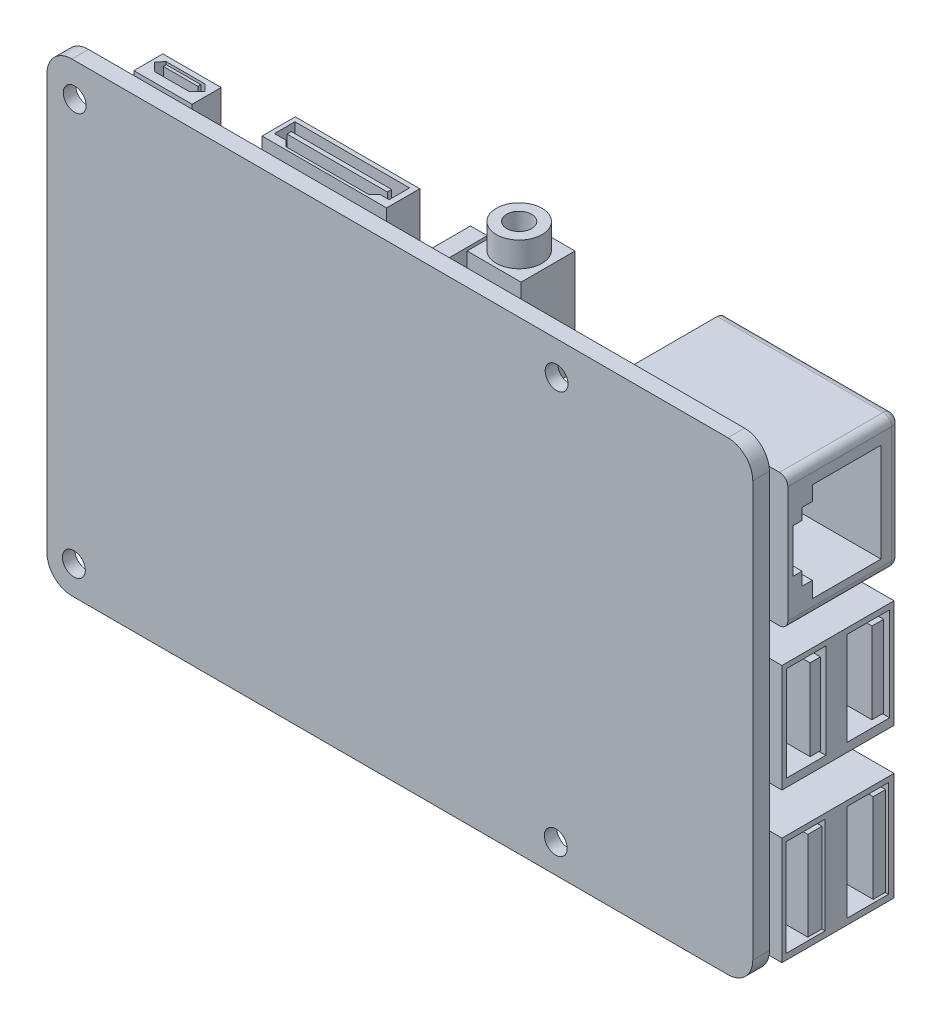
SolidWorks part; units mm, degrees
ref_plane "Front Plane" through (0, 0, 0) normal (0, 0, 1) x (1, 0, 0)
ref_plane "Top Plane" through (0, 0, 0) normal (0, 1, 0) x (1, 0, 0)
ref_plane "Right Plane" through (0, 0, 0) normal (1, 0, 0) x (0, 0, -1)
sketch "Sketch1" plane through (0, 0, 0) normal (0, 0, 1) x (1, 0, 0)
  line L1 (-42.5, 28) -> (42.5, 28)
  line L2 (-42.5, 28) -> (-42.5, -28)
  line L3 (-42.5, -28) -> (42.5, -28)
  line L4 (42.5, 28) -> (42.5, -28)
  line L5 (-42.5, 28) -> (42.5, -28) construction
  line L6 (-42.5, -28) -> (42.5, 28) construction
  point P0 (0, 0)
  dimension "D1" = 85
  dimension "D2" = 56
extrude "Boss-Extrude1" add sketch "Sketch1" along normal blind 2
fillet "Fillet1" radius 3 4 edges at (42.5, -28, 1) (42.5, 28, 1) (-42.5, 28, 1) (-42.5, -28, 1)
sketch "Sketch2" plane through (0, 0, 0) normal (0, 0, -1) x (-1, 0, 0)
  circle A0 centre (39.161, -24.5985) radius 3.1
  circle A1 centre (-18.839, -24.5986) radius 3.1
  circle A2 centre (39.161, 23.9785) radius 3.1
  circle A3 centre (-18.839, 23.9761) radius 3.1
  dimension "D1" = 6.2
  dimension "D3" = 6.2
  dimension "D2" = 58
  dimension "D4" = 58
extrude "Cut-Extrude2" cut sketch "Sketch2" against normal blind 0.5
sketch "Sketch3" plane through (0, 0, 0.5) normal (0, 0, -1) x (-1, 0, 0)
  circle A0 centre (39.161, 23.9785) radius 1.375
  circle A1 centre (-18.8764, 23.9785) radius 1.375
  circle A2 centre (-18.7753, -24.5312) radius 1.375
  circle A3 centre (39.2622, -24.5312) radius 1.375
  dimension "D1" = 2.75
  dimension "D2" = 2.75
extrude "Cut-Extrude3" cut sketch "Sketch3" against normal blind 10.5
sketch "Sketch4" plane through (0, 0, 0) normal (0, 0, -1) x (-1, 0, 0)
  line L0 (-39.5, 28) -> (39.5, 28) construction
  line L1 (-23.7207, 9.5) -> (-44.7207, 9.5)
  line L2 (-23.7207, 9.5) -> (-23.7207, 25.5)
  line L3 (-23.7207, 25.5) -> (-44.7207, 25.5)
  line L4 (-44.7207, 9.5) -> (-44.7207, 25.5)
  line L5 (-23.7207, 9.5) -> (-44.7207, 25.5) construction
  line L6 (-23.7207, 25.5) -> (-44.7207, 9.5) construction
  point P0 (-34.2207, 17.5)
  dimension "D1" = 2.5
  dimension "D2" = 21
  dimension "D3" = 16
  dimension "D4" = 10.5
extrude "Boss-Extrude2" add sketch "Sketch4" along normal blind 13.5
fillet "Fillet2" radius 1 5 edges at (34.2207, 25.5, -13.5) (34.2207, 9.5, -13.5) (44.7207, 9.5, -6.75) (44.7207, 25.5, -6.75) (44.7207, 17.5, -13.5)
sketch "Sketch5" plane through (44.7207, 0, 0) normal (1, 0, 0) x (0, 0, -1)
  line L0 (0.6237, 20.117) -> (0.6237, 14.8349)
  line L1 (0.6237, 14.8349) -> (1.7111, 14.8349)
  line L2 (1.7111, 14.8349) -> (1.7111, 13.2605)
  line L3 (1.7111, 13.2605) -> (2.9538, 13.2605)
  line L4 (2.9538, 13.2605) -> (2.9538, 11.3427)
  line L5 (2.9538, 11.3427) -> (11.2173, 11.3427)
  line L6 (11.2173, 11.3427) -> (11.2173, 23.2197)
  line L7 (11.2173, 23.2197) -> (2.9538, 23.2197)
  line L8 (2.9538, 23.2197) -> (2.9538, 21.4786)
  line L9 (2.9538, 21.4786) -> (1.7111, 21.4786)
  line L10 (1.7111, 21.4786) -> (1.7111, 20.117)
  line L11 (1.7111, 20.117) -> (0.6237, 20.117)
extrude "Cut-Extrude4" cut sketch "Sketch5" against normal blind 18.5
sketch "Sketch7" plane through (0, 0, 0) normal (0, 0, -1) x (-1, 0, 0)
  line L0 (-39.5, 28) -> (39.5, 28) construction
  line L1 (-44.0111, 5.5) -> (-27.0111, 5.5)
  line L2 (-44.0111, 5.5) -> (-44.0111, -7.5)
  line L3 (-44.0111, -7.5) -> (-27.0111, -7.5)
  line L4 (-27.0111, 5.5) -> (-27.0111, -7.5)
  line L5 (-44.0111, 5.5) -> (-27.0111, -7.5) construction
  line L6 (-44.0111, -7.5) -> (-27.0111, 5.5) construction
  point P0 (-35.5111, -1)
  dimension "D1" = 29
  dimension "D2" = 13
  dimension "D3" = 17
extrude "Boss-Extrude3" add sketch "Sketch7" along normal blind 13.5
sketch "Sketch8" plane through (44.0111, 0, 0) normal (1, 0, 0) x (0, 0, -1)
  line L1 (7.8471, 4.8156) -> (12.9735, 4.8156)
  line L2 (7.8471, 4.8156) -> (7.8471, -6.4468)
  line L3 (7.8471, -6.4468) -> (12.9735, -6.4468)
  line L4 (12.9735, 4.8156) -> (12.9735, -6.4468)
  line L5 (7.8471, 4.8156) -> (12.9735, -6.4468) construction
  line L6 (7.8471, -6.4468) -> (12.9735, 4.8156) construction
  line L7 (0.546, 4.8933) -> (5.284, 4.8933)
  line L8 (0.546, 4.8933) -> (0.546, -6.5244)
  line L9 (0.546, -6.5244) -> (5.284, -6.5244)
  line L10 (5.284, 4.8933) -> (5.284, -6.5244)
  line L11 (0.546, 4.8933) -> (5.284, -6.5244) construction
  line L12 (0.546, -6.5244) -> (5.284, 4.8933) construction
  point P0 (10.4103, -0.8156)
  point P5 (2.915, -0.8156)
extrude "Cut-Extrude5" cut sketch "Sketch8" against normal blind 13.5
sketch "Sketch9" plane through (30.5111, 0, 0) normal (1, 0, 0) x (0, 0, -1)
  line L1 (10.8479, 4.1943) -> (12.246, 4.1943)
  line L2 (10.8479, 4.1943) -> (10.8479, -5.5924)
  line L3 (10.8479, -5.5924) -> (12.246, -5.5924)
  line L4 (12.246, 4.1943) -> (12.246, -5.5924)
  line L5 (10.8479, 4.1943) -> (12.246, -5.5924) construction
  line L6 (10.8479, -5.5924) -> (12.246, 4.1943) construction
  line L7 (3.3914, 4.0778) -> (4.6341, 4.0778)
  line L8 (3.3914, 4.0778) -> (3.3914, -5.7089)
  line L9 (3.3914, -5.7089) -> (4.6341, -5.7089)
  line L10 (4.6341, 4.0778) -> (4.6341, -5.7089)
  line L11 (3.3914, 4.0778) -> (4.6341, -5.7089) construction
  line L12 (3.3914, -5.7089) -> (4.6341, 4.0778) construction
  point P0 (11.5469, -0.699)
  point P5 (4.0128, -0.8156)
  dimension "D1" = 0.6214
extrude "Boss-Extrude4" add sketch "Sketch9" along normal blind 13.5
sketch "Sketch10" plane through (0, 0, 0) normal (0, 0, -1) x (-1, 0, 0)
  line L0 (-39.5, 28) -> (39.5, 28) construction
  line L1 (-44.0178, -12.5) -> (-27.0044, -12.5)
  line L2 (-44.0178, -12.5) -> (-44.0178, -25.5)
  line L3 (-44.0178, -25.5) -> (-27.0044, -25.5)
  line L4 (-27.0044, -12.5) -> (-27.0044, -25.5)
  line L5 (-44.0178, -12.5) -> (-27.0044, -25.5) construction
  line L6 (-44.0178, -25.5) -> (-27.0044, -12.5) construction
  point P0 (-35.5111, -19)
  dimension "D1" = 47
  dimension "D2" = 13
  dimension "D3" = 17.0134
extrude "Boss-Extrude5" add sketch "Sketch10" along normal blind 13.5
sketch "Sketch11" plane through (44.0178, 0, 0) normal (1, 0, 0) x (0, 0, -1)
  line L1 (7.8471, -13.1265) -> (12.8181, -13.1265)
  line L2 (7.8471, -13.1265) -> (7.8471, -24.7773)
  line L3 (7.8471, -24.7773) -> (12.8181, -24.7773)
  line L4 (12.8181, -13.1265) -> (12.8181, -24.7773)
  line L5 (7.8471, -13.1265) -> (12.8181, -24.7773) construction
  line L6 (7.8471, -24.7773) -> (12.8181, -13.1265) construction
  line L7 (0.4891, -13.1265) -> (5.2063, -13.1265)
  line L8 (0.4891, -13.1265) -> (0.4891, -24.7773)
  line L9 (0.4891, -24.7773) -> (5.2063, -24.7773)
  line L10 (5.2063, -13.1265) -> (5.2063, -24.7773)
  line L11 (0.4891, -13.1265) -> (5.2063, -24.7773) construction
  line L12 (0.4891, -24.7773) -> (5.2063, -13.1265) construction
  point P0 (10.3326, -18.9519)
  point P5 (2.8477, -18.9519)
extrude "Cut-Extrude6" cut sketch "Sketch11" against normal blind 13.5
sketch "Sketch12" plane through (30.5178, 0, 0) normal (1, 0, 0) x (0, 0, -1)
  line L1 (12.479, -13.6702) -> (10.9825, -13.6702)
  line L2 (12.479, -13.6702) -> (12.479, -24.3889)
  line L3 (12.479, -24.3889) -> (10.9825, -24.3889)
  line L4 (10.9825, -13.6702) -> (10.9825, -24.3889)
  line L5 (12.479, -13.6702) -> (10.9825, -24.3889) construction
  line L6 (12.479, -24.3889) -> (10.9825, -13.6702) construction
  line L7 (3.1092, -13.6702) -> (4.8168, -13.6702)
  line L8 (3.1092, -13.6702) -> (3.1092, -24.3889)
  line L9 (3.1092, -24.3889) -> (4.8168, -24.3889)
  line L10 (4.8168, -13.6702) -> (4.8168, -24.3889)
  line L11 (3.1092, -13.6702) -> (4.8168, -24.3889) construction
  line L12 (3.1092, -24.3889) -> (4.8168, -13.6702) construction
  point P0 (11.7307, -19.0296)
  point P6 (3.963, -19.0296)
extrude "Boss-Extrude6" add sketch "Sketch12" along normal blind 13.5
sketch "Sketch13" plane through (0, 0, 0) normal (0, 0, -1) x (-1, 0, 0)
  line L0 (42.5, 25) -> (42.5, -25) construction
  line L1 (-14.0854, -22.7565) -> (35.0854, -22.7565)
  line L2 (-14.0854, -22.7565) -> (-14.0854, -27.2565)
  line L3 (-14.0854, -27.2565) -> (35.0854, -27.2565)
  line L4 (35.0854, -22.7565) -> (35.0854, -27.2565)
  line L5 (-14.0854, -22.7565) -> (35.0854, -27.2565) construction
  line L6 (-14.0854, -27.2565) -> (35.0854, -22.7565) construction
  point P0 (10.5, -25.0065)
  dimension "D1" = 32
  dimension "D2" = 4.5
extrude "Boss-Extrude7" add sketch "Sketch13" along normal blind 2.5
sketch "Sketch14" plane through (0, 0, -2.5) normal (0, 0, -1) x (-1, 0, 0)
  line L0 (-11.0708, -26.0079) -> (-10.1069, -26.0079)
  line L1 (-13.5708, -26.0079) -> (-12.6069, -26.0079)
  line L2 (-13.5708, -26.0079) -> (-13.5708, -27.0079)
  line L3 (-13.5708, -27.0079) -> (-12.6069, -27.0079)
  line L4 (-12.6069, -26.0079) -> (-12.6069, -27.0079)
  line L5 (-13.5708, -26.0079) -> (-12.6069, -27.0079) construction
  line L6 (-13.5708, -27.0079) -> (-12.6069, -26.0079) construction
  line L7 (-10.1069, -26.0079) -> (-10.1069, -27.0079)
  line L8 (-11.0708, -27.0079) -> (-10.1069, -27.0079)
  line L9 (-11.0708, -26.0079) -> (-11.0708, -27.0079)
  line L10 (-8.5708, -26.0079) -> (-7.6069, -26.0079)
  line L11 (-7.6069, -26.0079) -> (-7.6069, -27.0079)
  line L12 (-8.5708, -27.0079) -> (-7.6069, -27.0079)
  line L13 (-8.5708, -26.0079) -> (-8.5708, -27.0079)
  line L14 (-6.0708, -26.0079) -> (-5.1069, -26.0079)
  line L15 (-5.1069, -26.0079) -> (-5.1069, -27.0079)
  line L16 (-6.0708, -27.0079) -> (-5.1069, -27.0079)
  line L17 (-6.0708, -26.0079) -> (-6.0708, -27.0079)
  line L18 (-3.5708, -26.0079) -> (-2.6069, -26.0079)
  line L19 (-2.6069, -26.0079) -> (-2.6069, -27.0079)
  line L20 (-3.5708, -27.0079) -> (-2.6069, -27.0079)
  line L21 (-3.5708, -26.0079) -> (-3.5708, -27.0079)
  line L22 (-1.0708, -26.0079) -> (-0.1069, -26.0079)
  line L23 (-0.1069, -26.0079) -> (-0.1069, -27.0079)
  line L24 (-1.0708, -27.0079) -> (-0.1069, -27.0079)
  line L25 (-1.0708, -26.0079) -> (-1.0708, -27.0079)
  line L26 (1.4292, -26.0079) -> (2.3931, -26.0079)
  line L27 (2.3931, -26.0079) -> (2.3931, -27.0079)
  line L28 (1.4292, -27.0079) -> (2.3931, -27.0079)
  line L29 (1.4292, -26.0079) -> (1.4292, -27.0079)
  line L30 (3.9292, -26.0079) -> (4.8931, -26.0079)
  line L31 (4.8931, -26.0079) -> (4.8931, -27.0079)
  line L32 (3.9292, -27.0079) -> (4.8931, -27.0079)
  line L33 (3.9292, -26.0079) -> (3.9292, -27.0079)
  line L34 (6.4292, -26.0079) -> (7.3931, -26.0079)
  line L35 (7.3931, -26.0079) -> (7.3931, -27.0079)
  line L36 (6.4292, -27.0079) -> (7.3931, -27.0079)
  line L37 (6.4292, -26.0079) -> (6.4292, -27.0079)
  line L38 (8.9292, -26.0079) -> (9.8931, -26.0079)
  line L39 (9.8931, -26.0079) -> (9.8931, -27.0079)
  line L40 (8.9292, -27.0079) -> (9.8931, -27.0079)
  line L41 (8.9292, -26.0079) -> (8.9292, -27.0079)
  line L42 (11.4292, -26.0079) -> (12.3931, -26.0079)
  line L43 (12.3931, -26.0079) -> (12.3931, -27.0079)
  line L44 (11.4292, -27.0079) -> (12.3931, -27.0079)
  line L45 (11.4292, -26.0079) -> (11.4292, -27.0079)
  line L46 (13.9292, -26.0079) -> (14.8931, -26.0079)
  line L47 (14.8931, -26.0079) -> (14.8931, -27.0079)
  line L48 (13.9292, -27.0079) -> (14.8931, -27.0079)
  line L49 (13.9292, -26.0079) -> (13.9292, -27.0079)
  line L50 (16.4292, -26.0079) -> (17.3931, -26.0079)
  line L51 (17.3931, -26.0079) -> (17.3931, -27.0079)
  line L52 (16.4292, -27.0079) -> (17.3931, -27.0079)
  line L53 (16.4292, -26.0079) -> (16.4292, -27.0079)
  line L54 (18.9292, -26.0079) -> (19.8931, -26.0079)
  line L55 (19.8931, -26.0079) -> (19.8931, -27.0079)
  line L56 (18.9292, -27.0079) -> (19.8931, -27.0079)
  line L57 (18.9292, -26.0079) -> (18.9292, -27.0079)
  line L58 (21.4292, -26.0079) -> (22.3931, -26.0079)
  line L59 (22.3931, -26.0079) -> (22.3931, -27.0079)
  line L60 (21.4292, -27.0079) -> (22.3931, -27.0079)
  line L61 (21.4292, -26.0079) -> (21.4292, -27.0079)
  line L62 (23.9292, -26.0079) -> (24.8931, -26.0079)
  line L63 (24.8931, -26.0079) -> (24.8931, -27.0079)
  line L64 (23.9292, -27.0079) -> (24.8931, -27.0079)
  line L65 (23.9292, -26.0079) -> (23.9292, -27.0079)
  line L66 (26.4292, -26.0079) -> (27.3931, -26.0079)
  line L67 (27.3931, -26.0079) -> (27.3931, -27.0079)
  line L68 (26.4292, -27.0079) -> (27.3931, -27.0079)
  line L69 (26.4292, -26.0079) -> (26.4292, -27.0079)
  line L70 (28.9292, -26.0079) -> (29.8931, -26.0079)
  line L71 (29.8931, -26.0079) -> (29.8931, -27.0079)
  line L72 (28.9292, -27.0079) -> (29.8931, -27.0079)
  line L73 (28.9292, -26.0079) -> (28.9292, -27.0079)
  line L74 (31.4292, -26.0079) -> (32.3931, -26.0079)
  line L75 (32.3931, -26.0079) -> (32.3931, -27.0079)
  line L76 (31.4292, -27.0079) -> (32.3931, -27.0079)
  line L77 (31.4292, -26.0079) -> (31.4292, -27.0079)
  line L78 (33.9292, -26.0079) -> (34.8931, -26.0079)
  line L79 (34.8931, -26.0079) -> (34.8931, -27.0079)
  line L80 (33.9292, -27.0079) -> (34.8931, -27.0079)
  line L81 (33.9292, -26.0079) -> (33.9292, -27.0079)
  line L82 (1.4292, -23.0147) -> (1.4292, -24.0147)
  line L83 (26.4292, -23.0147) -> (27.3931, -23.0147)
  line L84 (31.4292, -23.0147) -> (32.3931, -23.0147)
  line L85 (-7.6069, -23.0147) -> (-7.6069, -24.0147)
  line L86 (-3.5708, -24.0147) -> (-2.6069, -24.0147)
  line L87 (-1.0708, -23.0147) -> (-1.0708, -24.0147)
  line L88 (8.9292, -23.0147) -> (9.8931, -23.0147)
  line L89 (13.9292, -23.0147) -> (14.8931, -23.0147)
  line L90 (13.9292, -24.0147) -> (14.8931, -24.0147)
  line L91 (16.4292, -23.0147) -> (17.3931, -23.0147)
  line L92 (11.4292, -23.0147) -> (11.4292, -24.0147)
  line L93 (21.4292, -24.0147) -> (22.3931, -24.0147)
  line L94 (34.8931, -23.0147) -> (34.8931, -24.0147)
  line L95 (-11.0708, -24.0147) -> (-10.1069, -24.0147)
  line L96 (-0.1069, -23.0147) -> (-0.1069, -24.0147)
  line L97 (6.4292, -24.0147) -> (7.3931, -24.0147)
  line L98 (21.4292, -23.0147) -> (21.4292, -24.0147)
  line L99 (27.3931, -23.0147) -> (27.3931, -24.0147)
  line L100 (3.9292, -23.0147) -> (4.8931, -23.0147)
  line L101 (16.4292, -23.0147) -> (16.4292, -24.0147)
  line L102 (32.3931, -23.0147) -> (32.3931, -24.0147)
  line L103 (-13.5708, -23.0147) -> (-12.6069, -23.0147)
  line L104 (3.9292, -24.0147) -> (4.8931, -24.0147)
  line L105 (3.9292, -23.0147) -> (3.9292, -24.0147)
  line L106 (11.4292, -23.0147) -> (12.3931, -23.0147)
  line L107 (11.4292, -24.0147) -> (12.3931, -24.0147)
  line L108 (18.9292, -23.0147) -> (18.9292, -24.0147)
  line L109 (26.4292, -23.0147) -> (26.4292, -24.0147)
  line L110 (-13.5708, -24.0147) -> (-12.6069, -24.0147)
  line L111 (-5.1069, -23.0147) -> (-5.1069, -24.0147)
  line L112 (21.4292, -23.0147) -> (22.3931, -23.0147)
  line L113 (26.4292, -24.0147) -> (27.3931, -24.0147)
  line L114 (-2.6069, -23.0147) -> (-2.6069, -24.0147)
  line L115 (1.4292, -24.0147) -> (2.3931, -24.0147)
  line L116 (6.4292, -23.0147) -> (7.3931, -23.0147)
  line L117 (8.9292, -23.0147) -> (8.9292, -24.0147)
  line L118 (23.9292, -23.0147) -> (23.9292, -24.0147)
  line L119 (28.9292, -23.0147) -> (29.8931, -23.0147)
  line L120 (-13.5708, -23.0147) -> (-12.6069, -24.0147) construction
  line L121 (-11.0708, -23.0147) -> (-11.0708, -24.0147)
  line L122 (-8.5708, -24.0147) -> (-7.6069, -24.0147)
  line L123 (-6.0708, -23.0147) -> (-6.0708, -24.0147)
  line L124 (-1.0708, -24.0147) -> (-0.1069, -24.0147)
  line L125 (6.4292, -23.0147) -> (6.4292, -24.0147)
  line L126 (8.9292, -24.0147) -> (9.8931, -24.0147)
  line L127 (24.8931, -23.0147) -> (24.8931, -24.0147)
  line L128 (33.9292, -24.0147) -> (34.8931, -24.0147)
  line L129 (18.9292, -23.0147) -> (19.8931, -23.0147)
  line L130 (31.4292, -23.0147) -> (31.4292, -24.0147)
  line L131 (-10.1069, -23.0147) -> (-10.1069, -24.0147)
  line L132 (-3.5708, -23.0147) -> (-3.5708, -24.0147)
  line L133 (7.3931, -23.0147) -> (7.3931, -24.0147)
  line L134 (12.3931, -23.0147) -> (12.3931, -24.0147)
  line L135 (13.9292, -23.0147) -> (13.9292, -24.0147)
  line L136 (23.9292, -23.0147) -> (24.8931, -23.0147)
  line L137 (-12.6069, -23.0147) -> (-12.6069, -24.0147)
  line L138 (16.4292, -24.0147) -> (17.3931, -24.0147)
  line L139 (29.8931, -23.0147) -> (29.8931, -24.0147)
  line L140 (-11.0708, -23.0147) -> (-10.1069, -23.0147)
  line L141 (-6.0708, -23.0147) -> (-5.1069, -23.0147)
  line L142 (9.8931, -23.0147) -> (9.8931, -24.0147)
  line L143 (17.3931, -23.0147) -> (17.3931, -24.0147)
  line L144 (28.9292, -24.0147) -> (29.8931, -24.0147)
  line L145 (33.9292, -23.0147) -> (33.9292, -24.0147)
  line L146 (-8.5708, -23.0147) -> (-7.6069, -23.0147)
  line L147 (-8.5708, -23.0147) -> (-8.5708, -24.0147)
  line L148 (23.9292, -24.0147) -> (24.8931, -24.0147)
  line L149 (31.4292, -24.0147) -> (32.3931, -24.0147)
  line L150 (-3.5708, -23.0147) -> (-2.6069, -23.0147)
  line L151 (2.3931, -23.0147) -> (2.3931, -24.0147)
  line L152 (18.9292, -24.0147) -> (19.8931, -24.0147)
  line L153 (33.9292, -23.0147) -> (34.8931, -23.0147)
  line L154 (-1.0708, -23.0147) -> (-0.1069, -23.0147)
  line L155 (4.8931, -23.0147) -> (4.8931, -24.0147)
  line L156 (19.8931, -23.0147) -> (19.8931, -24.0147)
  line L157 (22.3931, -23.0147) -> (22.3931, -24.0147)
  line L158 (-13.5708, -24.0147) -> (-12.6069, -23.0147) construction
  line L159 (-13.5708, -23.0147) -> (-13.5708, -24.0147)
  line L160 (-6.0708, -24.0147) -> (-5.1069, -24.0147)
  line L161 (1.4292, -23.0147) -> (2.3931, -23.0147)
  line L162 (14.8931, -23.0147) -> (14.8931, -24.0147)
  line L163 (28.9292, -23.0147) -> (28.9292, -24.0147)
  point P0 (-13.0889, -26.5079)
  point P6 (-13.0889, -23.5147)
  dimension "D1" = 0.9639
  dimension "D2" = 1
  dimension "D4" = 0.9639
  dimension "D5" = 1
  dimension "D3" = 20
extrude "Cut-Extrude7" cut sketch "Sketch14" against normal blind 2.5
sketch "Sketch15" plane through (0, 0, -2.5) normal (0, 0, -1) x (-1, 0, 0)
  line L0 (-12.6069, -27.0079) -> (-12.6069, -26.0079) construction
  line L1 (-13.5708, -26.0079) -> (-12.6069, -26.0079)
  line L2 (-13.5708, -26.0079) -> (-13.5708, -27.0079)
  line L3 (-13.5708, -27.0079) -> (-12.6069, -27.0079)
  line L4 (-12.6069, -26.0079) -> (-12.6069, -27.0079)
  line L5 (-13.5708, -26.0079) -> (-12.6069, -27.0079) construction
  line L6 (-13.5708, -27.0079) -> (-12.6069, -26.0079) construction
  line L7 (-13.5708, -27.0079) -> (-12.6069, -27.0079) construction
  line L8 (-12.6069, -26.0079) -> (-13.5708, -26.0079) construction
  line L9 (-13.5708, -26.0079) -> (-13.5708, -27.0079) construction
  line L10 (-11.0708, -26.0079) -> (-10.1069, -26.0079)
  line L11 (-10.1069, -26.0079) -> (-10.1069, -27.0079)
  line L12 (-11.0708, -27.0079) -> (-10.1069, -27.0079)
  line L13 (-11.0708, -26.0079) -> (-11.0708, -27.0079)
  line L14 (-8.5708, -26.0079) -> (-7.6069, -26.0079)
  line L15 (-7.6069, -26.0079) -> (-7.6069, -27.0079)
  line L16 (-8.5708, -27.0079) -> (-7.6069, -27.0079)
  line L17 (-8.5708, -26.0079) -> (-8.5708, -27.0079)
  line L18 (-6.0708, -26.0079) -> (-5.1069, -26.0079)
  line L19 (-5.1069, -26.0079) -> (-5.1069, -27.0079)
  line L20 (-6.0708, -27.0079) -> (-5.1069, -27.0079)
  line L21 (-6.0708, -26.0079) -> (-6.0708, -27.0079)
  line L22 (-3.5708, -26.0079) -> (-2.6069, -26.0079)
  line L23 (-2.6069, -26.0079) -> (-2.6069, -27.0079)
  line L24 (-3.5708, -27.0079) -> (-2.6069, -27.0079)
  line L25 (-3.5708, -26.0079) -> (-3.5708, -27.0079)
  line L26 (-1.0708, -26.0079) -> (-0.1069, -26.0079)
  line L27 (-0.1069, -26.0079) -> (-0.1069, -27.0079)
  line L28 (-1.0708, -27.0079) -> (-0.1069, -27.0079)
  line L29 (-1.0708, -26.0079) -> (-1.0708, -27.0079)
  line L30 (1.4292, -26.0079) -> (2.3931, -26.0079)
  line L31 (2.3931, -26.0079) -> (2.3931, -27.0079)
  line L32 (1.4292, -27.0079) -> (2.3931, -27.0079)
  line L33 (1.4292, -26.0079) -> (1.4292, -27.0079)
  line L34 (3.9292, -26.0079) -> (4.8931, -26.0079)
  line L35 (4.8931, -26.0079) -> (4.8931, -27.0079)
  line L36 (3.9292, -27.0079) -> (4.8931, -27.0079)
  line L37 (3.9292, -26.0079) -> (3.9292, -27.0079)
  line L38 (6.4292, -26.0079) -> (7.3931, -26.0079)
  line L39 (7.3931, -26.0079) -> (7.3931, -27.0079)
  line L40 (6.4292, -27.0079) -> (7.3931, -27.0079)
  line L41 (6.4292, -26.0079) -> (6.4292, -27.0079)
  line L42 (8.9292, -26.0079) -> (9.8931, -26.0079)
  line L43 (9.8931, -26.0079) -> (9.8931, -27.0079)
  line L44 (8.9292, -27.0079) -> (9.8931, -27.0079)
  line L45 (8.9292, -26.0079) -> (8.9292, -27.0079)
  line L46 (11.4292, -26.0079) -> (12.3931, -26.0079)
  line L47 (12.3931, -26.0079) -> (12.3931, -27.0079)
  line L48 (11.4292, -27.0079) -> (12.3931, -27.0079)
  line L49 (11.4292, -26.0079) -> (11.4292, -27.0079)
  line L50 (13.9292, -26.0079) -> (14.8931, -26.0079)
  line L51 (14.8931, -26.0079) -> (14.8931, -27.0079)
  line L52 (13.9292, -27.0079) -> (14.8931, -27.0079)
  line L53 (13.9292, -26.0079) -> (13.9292, -27.0079)
  line L54 (16.4292, -26.0079) -> (17.3931, -26.0079)
  line L55 (17.3931, -26.0079) -> (17.3931, -27.0079)
  line L56 (16.4292, -27.0079) -> (17.3931, -27.0079)
  line L57 (16.4292, -26.0079) -> (16.4292, -27.0079)
  line L58 (18.9292, -26.0079) -> (19.8931, -26.0079)
  line L59 (19.8931, -26.0079) -> (19.8931, -27.0079)
  line L60 (18.9292, -27.0079) -> (19.8931, -27.0079)
  line L61 (18.9292, -26.0079) -> (18.9292, -27.0079)
  line L62 (21.4292, -26.0079) -> (22.3931, -26.0079)
  line L63 (22.3931, -26.0079) -> (22.3931, -27.0079)
  line L64 (21.4292, -27.0079) -> (22.3931, -27.0079)
  line L65 (21.4292, -26.0079) -> (21.4292, -27.0079)
  line L66 (23.9292, -26.0079) -> (24.8931, -26.0079)
  line L67 (24.8931, -26.0079) -> (24.8931, -27.0079)
  line L68 (23.9292, -27.0079) -> (24.8931, -27.0079)
  line L69 (23.9292, -26.0079) -> (23.9292, -27.0079)
  line L70 (26.4292, -26.0079) -> (27.3931, -26.0079)
  line L71 (27.3931, -26.0079) -> (27.3931, -27.0079)
  line L72 (26.4292, -27.0079) -> (27.3931, -27.0079)
  line L73 (26.4292, -26.0079) -> (26.4292, -27.0079)
  line L74 (28.9292, -26.0079) -> (29.8931, -26.0079)
  line L75 (29.8931, -26.0079) -> (29.8931, -27.0079)
  line L76 (28.9292, -27.0079) -> (29.8931, -27.0079)
  line L77 (28.9292, -26.0079) -> (28.9292, -27.0079)
  line L78 (31.4292, -26.0079) -> (32.3931, -26.0079)
  line L79 (32.3931, -26.0079) -> (32.3931, -27.0079)
  line L80 (31.4292, -27.0079) -> (32.3931, -27.0079)
  line L81 (31.4292, -26.0079) -> (31.4292, -27.0079)
  line L82 (33.9292, -26.0079) -> (34.8931, -26.0079)
  line L83 (34.8931, -26.0079) -> (34.8931, -27.0079)
  line L84 (33.9292, -27.0079) -> (34.8931, -27.0079)
  line L85 (33.9292, -26.0079) -> (33.9292, -27.0079)
  line L86 (-13.5393, -24.0089) -> (-12.5753, -24.0089)
  line L87 (1.4607, -23.0089) -> (2.4247, -23.0089)
  line L88 (3.9607, -23.0089) -> (4.9247, -23.0089)
  line L89 (19.9247, -23.0089) -> (19.9247, -24.0089)
  line L90 (28.9607, -23.0089) -> (28.9607, -24.0089)
  line L91 (-6.0393, -23.0089) -> (-6.0393, -24.0089)
  line L92 (11.4607, -23.0089) -> (12.4247, -23.0089)
  line L93 (17.4247, -23.0089) -> (17.4247, -24.0089)
  line L94 (23.9607, -23.0089) -> (24.9247, -23.0089)
  line L95 (29.9247, -23.0089) -> (29.9247, -24.0089)
  line L96 (34.9247, -23.0089) -> (34.9247, -24.0089)
  line L97 (-0.0753, -23.0089) -> (-0.0753, -24.0089)
  line L98 (28.9607, -24.0089) -> (29.9247, -24.0089)
  line L99 (31.4607, -23.0089) -> (32.4247, -23.0089)
  line L100 (-13.5393, -23.0089) -> (-13.5393, -24.0089)
  line L101 (-8.5393, -23.0089) -> (-7.5753, -23.0089)
  line L102 (7.4247, -23.0089) -> (7.4247, -24.0089)
  line L103 (11.4607, -24.0089) -> (12.4247, -24.0089)
  line L104 (22.4247, -23.0089) -> (22.4247, -24.0089)
  line L105 (-3.5393, -24.0089) -> (-2.5753, -24.0089)
  line L106 (6.4607, -24.0089) -> (7.4247, -24.0089)
  line L107 (21.4607, -23.0089) -> (22.4247, -23.0089)
  line L108 (-12.5753, -23.0089) -> (-12.5753, -24.0089)
  line L109 (-7.5753, -23.0089) -> (-7.5753, -24.0089)
  line L110 (1.4607, -24.0089) -> (2.4247, -24.0089)
  line L111 (6.4607, -23.0089) -> (7.4247, -23.0089)
  line L112 (18.9607, -24.0089) -> (19.9247, -24.0089)
  line L113 (24.9247, -23.0089) -> (24.9247, -24.0089)
  line L114 (23.9607, -23.0089) -> (23.9607, -24.0089)
  line L115 (28.9607, -23.0089) -> (29.9247, -23.0089)
  line L116 (-8.5393, -24.0089) -> (-7.5753, -24.0089)
  line L117 (1.4607, -23.0089) -> (1.4607, -24.0089)
  line L118 (9.9247, -23.0089) -> (9.9247, -24.0089)
  line L119 (33.9607, -23.0089) -> (33.9607, -24.0089)
  line L120 (-1.0393, -24.0089) -> (-0.0753, -24.0089)
  line L121 (14.9247, -23.0089) -> (14.9247, -24.0089)
  line L122 (16.4607, -23.0089) -> (16.4607, -24.0089)
  line L123 (21.4607, -23.0089) -> (21.4607, -24.0089)
  line L124 (26.4607, -23.0089) -> (27.4247, -23.0089)
  line L125 (32.4247, -23.0089) -> (32.4247, -24.0089)
  line L126 (-5.0753, -23.0089) -> (-5.0753, -24.0089)
  line L127 (8.9607, -23.0089) -> (9.9247, -23.0089)
  line L128 (8.9607, -24.0089) -> (9.9247, -24.0089)
  line L129 (16.4607, -23.0089) -> (17.4247, -23.0089)
  line L130 (21.4607, -24.0089) -> (22.4247, -24.0089)
  line L131 (26.4607, -24.0089) -> (27.4247, -24.0089)
  line L132 (31.4607, -23.0089) -> (31.4607, -24.0089)
  line L133 (-3.5393, -23.0089) -> (-3.5393, -24.0089)
  line L134 (-13.5393, -23.0089) -> (-12.5753, -24.0089) construction
  line L135 (-11.0393, -23.0089) -> (-10.0753, -23.0089)
  line L136 (-8.5393, -23.0089) -> (-8.5393, -24.0089)
  line L137 (-3.5393, -23.0089) -> (-2.5753, -23.0089)
  line L138 (2.4247, -23.0089) -> (2.4247, -24.0089)
  line L139 (13.9607, -24.0089) -> (14.9247, -24.0089)
  line L140 (23.9607, -24.0089) -> (24.9247, -24.0089)
  line L141 (26.4607, -23.0089) -> (26.4607, -24.0089)
  line L142 (31.4607, -24.0089) -> (32.4247, -24.0089)
  line L143 (-13.5393, -23.0089) -> (-12.5753, -23.0089)
  line L144 (-2.5753, -23.0089) -> (-2.5753, -24.0089)
  line L145 (-1.0393, -23.0089) -> (-1.0393, -24.0089)
  line L146 (6.4607, -23.0089) -> (6.4607, -24.0089)
  line L147 (12.4247, -23.0089) -> (12.4247, -24.0089)
  line L148 (27.4247, -23.0089) -> (27.4247, -24.0089)
  line L149 (-11.0393, -24.0089) -> (-10.0753, -24.0089)
  line L150 (-6.0393, -24.0089) -> (-5.0753, -24.0089)
  line L151 (8.9607, -23.0089) -> (8.9607, -24.0089)
  line L152 (33.9607, -24.0089) -> (34.9247, -24.0089)
  line L153 (-13.5393, -24.0089) -> (-12.5753, -23.0089) construction
  line L154 (-1.0393, -23.0089) -> (-0.0753, -23.0089)
  line L155 (3.9607, -23.0089) -> (3.9607, -24.0089)
  line L156 (13.9607, -23.0089) -> (14.9247, -23.0089)
  line L157 (16.4607, -24.0089) -> (17.4247, -24.0089)
  line L158 (-10.0753, -23.0089) -> (-10.0753, -24.0089)
  line L159 (-6.0393, -23.0089) -> (-5.0753, -23.0089)
  line L160 (4.9247, -23.0089) -> (4.9247, -24.0089)
  line L161 (13.9607, -23.0089) -> (13.9607, -24.0089)
  line L162 (18.9607, -23.0089) -> (18.9607, -24.0089)
  line L163 (33.9607, -23.0089) -> (34.9247, -23.0089)
  line L164 (-11.0393, -23.0089) -> (-11.0393, -24.0089)
  line L165 (3.9607, -24.0089) -> (4.9247, -24.0089)
  line L166 (11.4607, -23.0089) -> (11.4607, -24.0089)
  line L167 (18.9607, -23.0089) -> (19.9247, -23.0089)
  point P0 (-13.0889, -26.5079)
  point P13 (-13.0573, -23.5089)
  dimension "D1" = 20
extrude "Boss-Extrude8" add sketch "Sketch15" along normal blind 5 and the other way blind 2.5
sketch "Sketch16" plane through (0, 0, 0) normal (0, 0, -1) x (-1, 0, 0)
  line L1 (9.1227, 6.5) -> (22.1227, 6.5)
  line L2 (9.1227, 6.5) -> (9.1227, -6.5)
  line L3 (9.1227, -6.5) -> (22.1227, -6.5)
  line L4 (22.1227, 6.5) -> (22.1227, -6.5)
  line L5 (9.1227, 6.5) -> (22.1227, -6.5) construction
  line L6 (9.1227, -6.5) -> (22.1227, 6.5) construction
  point P0 (15.6227, 0)
  dimension "D1" = 13
  dimension "D2" = 13
extrude "Boss-Extrude9" add sketch "Sketch16" along normal blind 1
sketch "Sketch17" plane through (0, 0, 0) normal (0, 0, -1) x (-1, 0, 0)
  line L1 (-19.4325, -1.3087) -> (-10.8323, -1.3087)
  line L2 (-19.4325, -1.3087) -> (-19.4325, -9.9089)
  line L3 (-19.4325, -9.9089) -> (-10.8323, -9.9089)
  line L4 (-10.8323, -1.3087) -> (-10.8323, -9.9089)
  line L5 (-19.4325, -1.3087) -> (-10.8323, -9.9089) construction
  line L6 (-19.4325, -9.9089) -> (-10.8323, -1.3087) construction
  point P0 (-15.1324, -5.6088)
extrude "Boss-Extrude10" add sketch "Sketch17" along normal blind 1
sketch "Sketch18" plane through (0, 0, 0) normal (0, 0, -1) x (-1, 0, 0)
  line L0 (38.9928, 10.2325) -> (41.0493, 10.2325)
  line L1 (41.0493, 10.2325) -> (41.0493, 8.7325)
  line L2 (41.0493, 8.7325) -> (42.2178, 7.564)
  line L3 (42.2178, 7.564) -> (42.2178, -4.436)
  line L4 (42.2178, -4.436) -> (41.0493, -5.6045)
  line L5 (41.0493, -5.6045) -> (41.0493, -7.1045)
  line L6 (41.0493, -7.1045) -> (38.9928, -7.1045)
  line L7 (38.9928, -7.1045) -> (38.9928, 10.2325)
  dimension "D1" = 12
  dimension "D2" = 1.5
  dimension "D3" = 1.5
extrude "Boss-Extrude11" add sketch "Sketch18" along normal blind 5
sketch "Sketch19" plane through (0, 0, -5) normal (0, 0, -1) x (-1, 0, 0)
  line L1 (39.2875, 8.3506) -> (40.3311, 8.3506)
  line L2 (39.2875, 8.3506) -> (39.2875, -5.0077)
  line L3 (39.2875, -5.0077) -> (40.3311, -5.0077)
  line L4 (40.3311, 8.3506) -> (40.3311, -5.0077)
  line L5 (39.2875, 8.3506) -> (40.3311, -5.0077) construction
  line L6 (39.2875, -5.0077) -> (40.3311, 8.3506) construction
  point P0 (39.8093, 1.6715)
extrude "Cut-Extrude8" cut sketch "Sketch19" against normal blind 5
sketch "Sketch20" plane through (0, 0, 0) normal (0, 0, -1) x (-1, 0, 0)
  line L1 (-12.5931, 29.7719) -> (-6.0931, 29.7719)
  line L2 (-12.5931, 29.7719) -> (-12.5931, 17.1703)
  line L3 (-12.5931, 17.1703) -> (-6.0931, 17.1703)
  line L4 (-6.0931, 29.7719) -> (-6.0931, 17.1703)
  line L5 (-12.5931, 29.7719) -> (-6.0931, 17.1703) construction
  line L6 (-12.5931, 17.1703) -> (-6.0931, 29.7719) construction
  point P0 (-9.3431, 23.4711)
  dimension "D1" = 6.5
extrude "Boss-Extrude12" add sketch "Sketch20" along normal blind 6.5
sketch "Sketch21" plane through (0, 29.7719, 0) normal (0, 1, 0) x (1, 0, 0)
  circle A0 centre (9.148, 3.2205) radius 2.75
  dimension "D1" = 5.5
extrude "Boss-Extrude13" add sketch "Sketch21" along normal blind 3
sketch "Sketch22" plane through (0, 32.7719, 0) normal (0, 1, 0) x (1, 0, 0)
  circle A0 centre (9.148, 3.2205) radius 1.5
  dimension "D1" = 3
extrude "Cut-Extrude9" cut sketch "Sketch22" against normal blind 15
sketch "Sketch23" plane through (0, 0, 0) normal (0, 0, -1) x (-1, 0, 0)
  line L0 (0, 10.0715) -> (-2.0282, 10.0715)
  line L1 (-2.0282, 10.0715) -> (-2.0282, 13.0527)
  line L2 (-2.0282, 13.0527) -> (-3.4986, 14.5231)
  line L3 (-3.4986, 14.5231) -> (-3.4986, 21.6187)
  line L4 (-3.4986, 21.6187) -> (-2.0282, 23.0891)
  line L5 (-2.0282, 23.0891) -> (-2.0282, 26.0817)
  line L6 (-2.0282, 26.0817) -> (0, 26.0817)
  line L7 (0, 26.0817) -> (0, 10.0715)
extrude "Boss-Extrude14" add sketch "Sketch23" along normal blind 6.5
sketch "Sketch24" plane through (0, 0, -6.5) normal (0, 0, -1) x (-1, 0, 0)
  line L1 (-0.4085, 13.3017) -> (-1.3834, 13.3017)
  line L2 (-0.4085, 13.3017) -> (-0.4085, 22.8986)
  line L3 (-0.4085, 22.8986) -> (-1.3834, 22.8986)
  line L4 (-1.3834, 13.3017) -> (-1.3834, 22.8986)
  line L5 (-0.4085, 13.3017) -> (-1.3834, 22.8986) construction
  line L6 (-0.4085, 22.8986) -> (-1.3834, 13.3017) construction
  point P0 (-0.896, 18.1001)
extrude "Cut-Extrude10" cut sketch "Sketch24" against normal blind 6.5
sketch "Sketch25" plane through (0, 0, 0) normal (0, 0, -1) x (-1, 0, 0)
  line L1 (18.6005, 17.4163) -> (3.6005, 17.4163)
  line L2 (18.6005, 17.4163) -> (18.6005, 29.4163)
  line L3 (18.6005, 29.4163) -> (3.6005, 29.4163)
  line L4 (3.6005, 17.4163) -> (3.6005, 29.4163)
  line L5 (18.6005, 17.4163) -> (3.6005, 29.4163) construction
  line L6 (18.6005, 29.4163) -> (3.6005, 17.4163) construction
  point P0 (11.1005, 23.4163)
  dimension "D1" = 15
  dimension "D2" = 12
extrude "Boss-Extrude15" add sketch "Sketch25" along normal blind 4
sketch "Sketch26" plane through (0, 29.4163, 0) normal (0, 1, 0) x (1, 0, 0)
  line L0 (-18.1055, 3.4713) -> (-4.2971, 3.4713)
  line L1 (-4.2971, 3.4713) -> (-4.2971, 1.0042)
  line L2 (-4.2971, 1.0042) -> (-5.3631, 1.0042)
  line L3 (-5.3631, 1.0042) -> (-6.045, 0.3222)
  line L4 (-6.045, 0.3222) -> (-16.0377, 0.3222)
  line L5 (-16.0377, 0.3222) -> (-16.7196, 1.0042)
  line L6 (-16.7196, 1.0042) -> (-18.1055, 1.0042)
  line L7 (-18.1055, 1.0042) -> (-18.1055, 3.4713)
extrude "Cut-Extrude11" cut sketch "Sketch26" against normal blind 11
sketch "Sketch27" plane through (0, 18.4163, 0) normal (0, 1, 0) x (1, 0, 0)
  line L1 (-17.2982, 2.2235) -> (-5.2204, 2.2235)
  line L2 (-17.2982, 2.2235) -> (-17.2982, 1.708)
  line L3 (-17.2982, 1.708) -> (-5.2204, 1.708)
  line L4 (-5.2204, 2.2235) -> (-5.2204, 1.708)
  line L5 (-17.2982, 2.2235) -> (-5.2204, 1.708) construction
  line L6 (-17.2982, 1.708) -> (-5.2204, 2.2235) construction
  point P0 (-11.2593, 1.9657)
extrude "Boss-Extrude16" add sketch "Sketch27" along normal blind 11
sketch "Sketch28" plane through (0, 0, 0) normal (0, 0, -1) x (-1, 0, 0)
  line L1 (34.0404, 22.6437) -> (27.0224, 22.6437)
  line L2 (34.0404, 22.6437) -> (34.0404, 28.5159)
  line L3 (34.0404, 28.5159) -> (27.0224, 28.5159)
  line L4 (27.0224, 22.6437) -> (27.0224, 28.5159)
  line L5 (34.0404, 22.6437) -> (27.0224, 28.5159) construction
  line L6 (34.0404, 28.5159) -> (27.0224, 22.6437) construction
  point P0 (30.5314, 25.5798)
extrude "Boss-Extrude17" add sketch "Sketch28" along normal blind 3.5
sketch "Sketch29" plane through (0, 28.5159, 0) normal (0, 1, 0) x (1, 0, 0)
  line L0 (-33.0397, 2.8909) -> (-28.3637, 2.8909)
  line L1 (-28.3637, 2.8909) -> (-27.5996, 2.1269)
  line L2 (-27.5996, 2.1269) -> (-28.5776, 1.1489)
  line L3 (-28.5776, 1.1489) -> (-32.7035, 1.1489)
  line L4 (-32.7035, 1.1489) -> (-33.6815, 2.1269)
  line L5 (-33.6815, 2.1269) -> (-33.0397, 2.8909)
extrude "Cut-Extrude12" cut sketch "Sketch29" against normal blind 5.5
sketch "Sketch30" plane through (0, 23.0159, 0) normal (0, 1, 0) x (1, 0, 0)
  line L1 (-32.7065, 2.5688) -> (-28.5473, 2.5688)
  line L2 (-32.7065, 2.5688) -> (-32.7065, 2.2193)
  line L3 (-32.7065, 2.2193) -> (-28.5473, 2.2193)
  line L4 (-28.5473, 2.5688) -> (-28.5473, 2.2193)
  line L5 (-32.7065, 2.5688) -> (-28.5473, 2.2193) construction
  line L6 (-32.7065, 2.2193) -> (-28.5473, 2.5688) construction
  point P0 (-30.6269, 2.394)
extrude "Boss-Extrude18" add sketch "Sketch30" along normal blind 5.5
sketch "Sketch31" plane through (0, 0, -1) normal (0, 0, -1) x (-1, 0, 0)
  line L0 (-10.8323, -1.3087) -> (-19.4325, -1.3087) construction
  line L1 (-19.1594, -0.8087) -> (-18.6594, -0.8087)
  line L2 (-19.1594, -0.8087) -> (-19.1594, -1.3087)
  line L3 (-19.1594, -1.3087) -> (-18.6594, -1.3087)
  line L4 (-18.6594, -0.8087) -> (-18.6594, -1.3087)
  line L5 (-19.1594, -0.8087) -> (-18.6594, -1.3087) construction
  line L6 (-19.1594, -1.3087) -> (-18.6594, -0.8087) construction
  line L7 (-18.1594, -0.8087) -> (-17.6594, -0.8087)
  line L8 (-17.6594, -0.8087) -> (-17.6594, -1.3087)
  line L9 (-18.1594, -1.3087) -> (-17.6594, -1.3087)
  line L10 (-18.1594, -0.8087) -> (-18.1594, -1.3087)
  line L11 (-17.1594, -0.8087) -> (-16.6594, -0.8087)
  line L12 (-16.6594, -0.8087) -> (-16.6594, -1.3087)
  line L13 (-17.1594, -1.3087) -> (-16.6594, -1.3087)
  line L14 (-17.1594, -0.8087) -> (-17.1594, -1.3087)
  line L15 (-16.1594, -0.8087) -> (-15.6594, -0.8087)
  line L16 (-15.6594, -0.8087) -> (-15.6594, -1.3087)
  line L17 (-16.1594, -1.3087) -> (-15.6594, -1.3087)
  line L18 (-16.1594, -0.8087) -> (-16.1594, -1.3087)
  line L19 (-15.1594, -0.8087) -> (-14.6594, -0.8087)
  line L20 (-14.6594, -0.8087) -> (-14.6594, -1.3087)
  line L21 (-15.1594, -1.3087) -> (-14.6594, -1.3087)
  line L22 (-15.1594, -0.8087) -> (-15.1594, -1.3087)
  line L23 (-14.1594, -0.8087) -> (-13.6594, -0.8087)
  line L24 (-13.6594, -0.8087) -> (-13.6594, -1.3087)
  line L25 (-14.1594, -1.3087) -> (-13.6594, -1.3087)
  line L26 (-14.1594, -0.8087) -> (-14.1594, -1.3087)
  line L27 (-13.1594, -0.8087) -> (-12.6594, -0.8087)
  line L28 (-12.6594, -0.8087) -> (-12.6594, -1.3087)
  line L29 (-13.1594, -1.3087) -> (-12.6594, -1.3087)
  line L30 (-13.1594, -0.8087) -> (-13.1594, -1.3087)
  line L31 (-12.1594, -0.8087) -> (-11.6594, -0.8087)
  line L32 (-11.6594, -0.8087) -> (-11.6594, -1.3087)
  line L33 (-12.1594, -1.3087) -> (-11.6594, -1.3087)
  line L34 (-12.1594, -0.8087) -> (-12.1594, -1.3087)
  line L35 (-18.9225, -9.9089) -> (-18.4225, -9.9089)
  line L36 (-15.4225, -9.9089) -> (-15.4225, -10.4089)
  line L37 (-18.4225, -9.9089) -> (-18.4225, -10.4089)
  line L38 (-12.9225, -10.4089) -> (-12.4225, -10.4089)
  line L39 (-11.4225, -9.9089) -> (-11.4225, -10.4089)
  line L40 (-14.9225, -9.9089) -> (-14.9225, -10.4089)
  line L41 (-14.9225, -9.9089) -> (-14.4225, -9.9089)
  line L42 (-12.4225, -9.9089) -> (-12.4225, -10.4089)
  line L43 (-16.4225, -9.9089) -> (-16.4225, -10.4089)
  line L44 (-14.9225, -10.4089) -> (-14.4225, -10.4089)
  line L45 (-18.9225, -10.4089) -> (-18.4225, -9.9089) construction
  line L46 (-14.4225, -9.9089) -> (-14.4225, -10.4089)
  line L47 (-11.9225, -10.4089) -> (-11.4225, -10.4089)
  line L48 (-18.9225, -9.9089) -> (-18.9225, -10.4089)
  line L49 (-17.4225, -9.9089) -> (-17.4225, -10.4089)
  line L50 (-13.9225, -9.9089) -> (-13.4225, -9.9089)
  line L51 (-13.9225, -10.4089) -> (-13.4225, -10.4089)
  line L52 (-12.9225, -9.9089) -> (-12.4225, -9.9089)
  line L53 (-16.9225, -10.4089) -> (-16.4225, -10.4089)
  line L54 (-13.9225, -9.9089) -> (-13.9225, -10.4089)
  line L55 (-17.9225, -9.9089) -> (-17.4225, -9.9089)
  line L56 (-13.4225, -9.9089) -> (-13.4225, -10.4089)
  line L57 (-17.9225, -9.9089) -> (-17.9225, -10.4089)
  line L58 (-11.9225, -9.9089) -> (-11.9225, -10.4089)
  line L59 (-17.9225, -10.4089) -> (-17.4225, -10.4089)
  line L60 (-16.9225, -9.9089) -> (-16.9225, -10.4089)
  line L61 (-18.9225, -10.4089) -> (-18.4225, -10.4089)
  line L62 (-15.9225, -10.4089) -> (-15.4225, -10.4089)
  line L63 (-11.9225, -9.9089) -> (-11.4225, -9.9089)
  line L64 (-15.9225, -9.9089) -> (-15.4225, -9.9089)
  line L65 (-15.9225, -9.9089) -> (-15.9225, -10.4089)
  line L66 (-12.9225, -9.9089) -> (-12.9225, -10.4089)
  line L67 (-16.9225, -9.9089) -> (-16.4225, -9.9089)
  line L68 (-18.9225, -9.9089) -> (-18.4225, -10.4089) construction
  line L69 (-19.4325, -9.9089) -> (-10.8323, -9.9089) construction
  line L70 (-19.4325, -1.3087) -> (-19.4325, -9.9089) construction
  line L71 (-19.9325, -1.4389) -> (-19.4325, -1.4389)
  line L72 (-19.9325, -1.4389) -> (-19.9325, -1.9389)
  line L73 (-19.9325, -1.9389) -> (-19.4325, -1.9389)
  line L74 (-19.4325, -1.4389) -> (-19.4325, -1.9389)
  line L75 (-19.9325, -1.4389) -> (-19.4325, -1.9389) construction
  line L76 (-19.9325, -1.9389) -> (-19.4325, -1.4389) construction
  line L77 (-19.9325, -2.5389) -> (-19.4325, -2.5389)
  line L78 (-19.9325, -3.0389) -> (-19.4325, -3.0389)
  line L79 (-19.9325, -2.5389) -> (-19.9325, -3.0389)
  line L80 (-19.4325, -2.5389) -> (-19.4325, -3.0389)
  line L81 (-19.9325, -3.6389) -> (-19.4325, -3.6389)
  line L82 (-19.9325, -4.1389) -> (-19.4325, -4.1389)
  line L83 (-19.9325, -3.6389) -> (-19.9325, -4.1389)
  line L84 (-19.4325, -3.6389) -> (-19.4325, -4.1389)
  line L85 (-19.9325, -4.7389) -> (-19.4325, -4.7389)
  line L86 (-19.9325, -5.2389) -> (-19.4325, -5.2389)
  line L87 (-19.9325, -4.7389) -> (-19.9325, -5.2389)
  line L88 (-19.4325, -4.7389) -> (-19.4325, -5.2389)
  line L89 (-19.9325, -5.8389) -> (-19.4325, -5.8389)
  line L90 (-19.9325, -6.3389) -> (-19.4325, -6.3389)
  line L91 (-19.9325, -5.8389) -> (-19.9325, -6.3389)
  line L92 (-19.4325, -5.8389) -> (-19.4325, -6.3389)
  line L93 (-19.9325, -6.9389) -> (-19.4325, -6.9389)
  line L94 (-19.9325, -7.4389) -> (-19.4325, -7.4389)
  line L95 (-19.9325, -6.9389) -> (-19.9325, -7.4389)
  line L96 (-19.4325, -6.9389) -> (-19.4325, -7.4389)
  line L97 (-19.9325, -8.0389) -> (-19.4325, -8.0389)
  line L98 (-19.9325, -8.5389) -> (-19.4325, -8.5389)
  line L99 (-19.9325, -8.0389) -> (-19.9325, -8.5389)
  line L100 (-19.4325, -8.0389) -> (-19.4325, -8.5389)
  line L101 (-19.9325, -9.1389) -> (-19.4325, -9.1389)
  line L102 (-19.9325, -9.6389) -> (-19.4325, -9.6389)
  line L103 (-19.9325, -9.1389) -> (-19.9325, -9.6389)
  line L104 (-19.4325, -9.1389) -> (-19.4325, -9.6389)
  line L105 (-10.8323, -9.9089) -> (-10.8323, -1.3087) construction
  line L106 (-10.8323, -1.3562) -> (-10.3323, -1.3562)
  line L107 (-10.8323, -1.3562) -> (-10.8323, -1.8562)
  line L108 (-10.8323, -1.8562) -> (-10.3323, -1.8562)
  line L109 (-10.3323, -1.3562) -> (-10.3323, -1.8562)
  line L110 (-10.8323, -1.3562) -> (-10.3323, -1.8562) construction
  line L111 (-10.8323, -1.8562) -> (-10.3323, -1.3562) construction
  line L112 (-10.8323, -2.4562) -> (-10.3323, -2.4562)
  line L113 (-10.3323, -2.4562) -> (-10.3323, -2.9562)
  line L114 (-10.8323, -2.9562) -> (-10.3323, -2.9562)
  line L115 (-10.8323, -2.4562) -> (-10.8323, -2.9562)
  line L116 (-10.8323, -3.5562) -> (-10.3323, -3.5562)
  line L117 (-10.3323, -3.5562) -> (-10.3323, -4.0562)
  line L118 (-10.8323, -4.0562) -> (-10.3323, -4.0562)
  line L119 (-10.8323, -3.5562) -> (-10.8323, -4.0562)
  line L120 (-10.8323, -4.6562) -> (-10.3323, -4.6562)
  line L121 (-10.3323, -4.6562) -> (-10.3323, -5.1562)
  line L122 (-10.8323, -5.1562) -> (-10.3323, -5.1562)
  line L123 (-10.8323, -4.6562) -> (-10.8323, -5.1562)
  line L124 (-10.8323, -5.7562) -> (-10.3323, -5.7562)
  line L125 (-10.3323, -5.7562) -> (-10.3323, -6.2562)
  line L126 (-10.8323, -6.2562) -> (-10.3323, -6.2562)
  line L127 (-10.8323, -5.7562) -> (-10.8323, -6.2562)
  line L128 (-10.8323, -6.8562) -> (-10.3323, -6.8562)
  line L129 (-10.3323, -6.8562) -> (-10.3323, -7.3562)
  line L130 (-10.8323, -7.3562) -> (-10.3323, -7.3562)
  line L131 (-10.8323, -6.8562) -> (-10.8323, -7.3562)
  line L132 (-10.8323, -7.9562) -> (-10.3323, -7.9562)
  line L133 (-10.3323, -7.9562) -> (-10.3323, -8.4562)
  line L134 (-10.8323, -8.4562) -> (-10.3323, -8.4562)
  line L135 (-10.8323, -7.9562) -> (-10.8323, -8.4562)
  line L136 (-10.8323, -9.0562) -> (-10.3323, -9.0562)
  line L137 (-10.3323, -9.0562) -> (-10.3323, -9.5562)
  line L138 (-10.8323, -9.5562) -> (-10.3323, -9.5562)
  line L139 (-10.8323, -9.0562) -> (-10.8323, -9.5562)
  point P0 (-18.9094, -1.0587)
  point P8 (-18.6725, -10.1184)
  point P70 (-19.6825, -1.6889)
  point P77 (-10.5823, -1.6062)
  dimension "D1" = 0.5
  dimension "D2" = 0.5
  dimension "D4" = 0.5
  dimension "D5" = 0.5
  dimension "D6" = 0.5
  dimension "D7" = 0.5
  dimension "D9" = 0.5
  dimension "D10" = 0.5
  dimension "D3" = 8
  dimension "D8" = 8
  dimension "D11" = 8
extrude "Boss-Extrude19" add sketch "Sketch31" against normal up to surface (1 mm away) up to face at (15.1324, -5.6088, 0)
sketch "Sketch32" plane through (0, 0, 0) normal (0, 0, -1) x (-1, 0, 0)
  text T0 "Raspberry Pi Model B+ V1.2"
extrude "Cut-Extrude13" cut sketch "Sketch32" against normal blind 1.1
